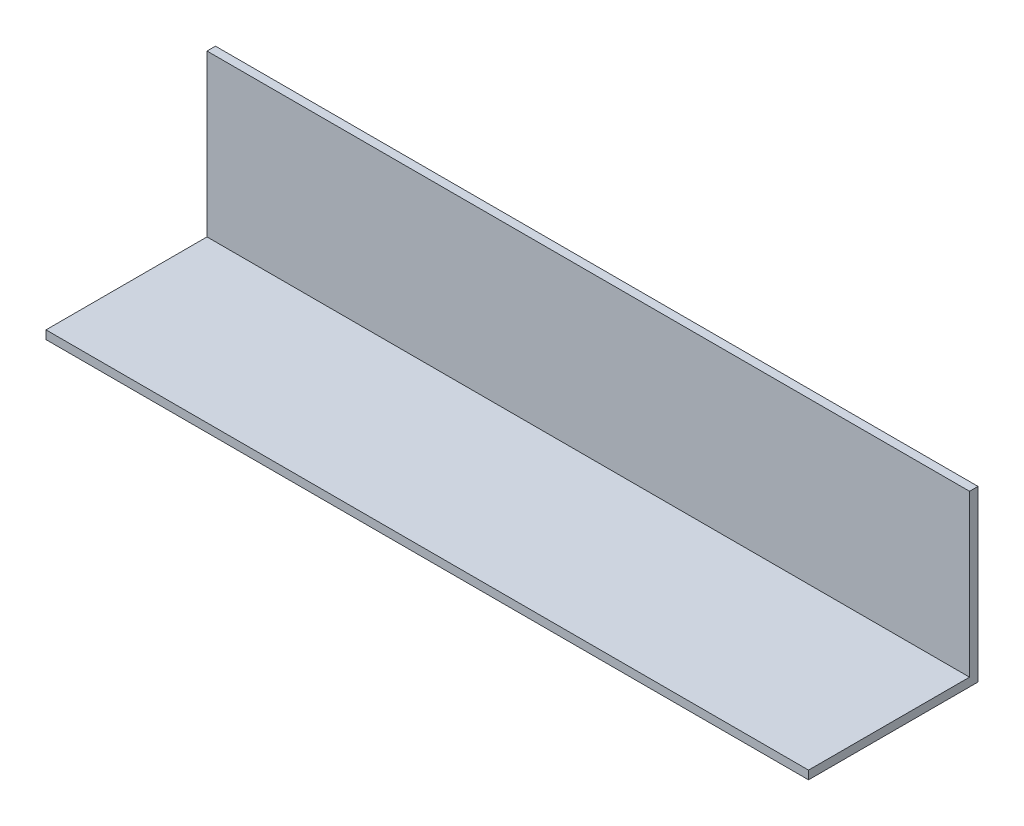
SolidWorks part; units mm, degrees
material "Monel(R) 400"
ref_plane "Front Plane" through (0, 0, 0) normal (0, 0, 1) x (1, 0, 0)
ref_plane "Top Plane" through (0, 0, 0) normal (0, 1, 0) x (1, 0, 0)
ref_plane "Right Plane" through (0, 0, 0) normal (1, 0, 0) x (0, 0, -1)
sketch "Sketch1" plane through (0, 0, 0) normal (0, 0, 1) x (1, 0, 0)
  line L0 (-223.52, 50.8) -> (-223.52, -50.8)
  line L1 (228.6, -50.8) -> (-228.6, -50.8)
  line L2 (228.6, -50.8) -> (228.6, 50.8)
  line L3 (228.6, 50.8) -> (-228.6, 50.8)
  line L4 (-228.6, -50.8) -> (-228.6, 50.8)
  line L5 (228.6, -50.8) -> (-228.6, 50.8) construction
  line L6 (228.6, 50.8) -> (-228.6, -50.8) construction
  line L7 (223.52, 50.8) -> (223.52, -50.8)
  line L8 (-228.6, -45.72) -> (228.6, -45.72)
  line L9 (-228.6, 45.72) -> (228.6, 45.72)
  point P0 (0, 0)
  dimension "D1" = 457.2
  dimension "D2" = 101.6
  dimension "D3" = 5.08
  dimension "D4" = 5.08
  dimension "D5" = 5.08
  dimension "D6" = 5.08
extrude "Boss-Extrude1" add sketch "Sketch1" along normal blind 5.08 contours L4 L3 L2 L1
extrude "Boss-Extrude2" add sketch "Sketch1<4>" along normal blind 101.6 contours L8 L7 L1 L2 | L8 L0 L1 L7 | L8 L4 L1 L0 region at (0, -48.26, 0) region at (-226.06, -48.26, 0) region at (226.06, -48.26, 0)
sketch "Sketch1<4>" plane through (0, 0, 0) normal (0, 0, 1) x (1, 0, 0) same geometry as "Sketch1"
